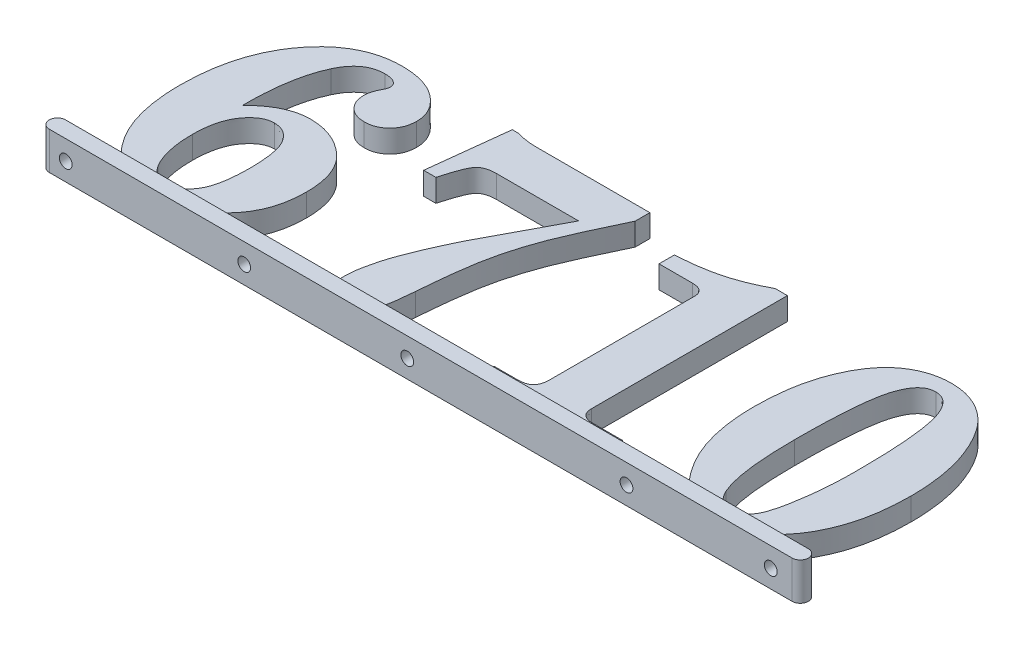
SolidWorks part; units mm, degrees
ref_plane "Front Plane" through (0, 0, 0) normal (0, 0, 1) x (1, 0, 0)
ref_plane "Top Plane" through (0, 0, 0) normal (0, 1, 0) x (1, 0, 0)
ref_plane "Right Plane" through (0, 0, 0) normal (1, 0, 0) x (0, 0, -1)
sketch "Sketch1" plane through (0, 0, 0) normal (0, 1, 0) x (1, 0, 0)
  text T0 "6710" font "Century Schoolbook" height 63.5
extrude "Boss-Extrude2" add sketch "Sketch1" along normal blind 6
sketch "Sketch2" plane through (0, 0, 0) normal (0, 1, 0) x (1, 0, 0)
  line L0 (-83.0987, -20.1486) -> (114.7244, -20.1486) construction
  line L1 (-83.0987, -17.9936) -> (114.7244, -17.9936)
  line L2 (-83.0987, -22.3035) -> (114.7244, -22.3035)
  arc A0 (-83.0987, -17.9936) -> (-83.0987, -22.3035) centre (-83.0987, -20.1486) ccw
  arc A1 (114.7244, -22.3035) -> (114.7244, -17.9936) centre (114.7244, -20.1486) ccw
  point P2 (15.8128, -20.1486)
extrude "Boss-Extrude3" add sketch "Sketch2" along normal blind 10
hole_wizard "M3 Clearance Hole1" positions "Sketch4" profile "Sketch3" hole size "M3" standard "ANSI Metric" end condition through all
sketch "Sketch4" plane through (0, 0, 17.9936) normal (0, 0, -1) x (-1, 0, 0)
  point P0 (78.7272, 4.7902)
  point P2 (31.1938, 4.7902)
  point P4 (-12.2208, 4.7902)
  point P6 (-70.6134, 4.7902)
  point P8 (-109.0334, 4.7902)
sketch "Sketch3" plane through (-78.7272, 4.7902, 17.9936) normal (1, 0, 0) x (0, 1, 0)
  line L0 (0, 0) -> (0, 4.3099)
  line L1 (0, 4.3099) -> (1.7, 4.3099)
  line L2 (1.7, 4.3099) -> (1.7, 0)
  line L5 (1.7, 0) -> (0, 0)
  line L11 (0, -6.35) -> (0, 107.95) construction
  dimension "Thru Hole Dia." = 3.4
  dimension "Thru Hole Depth" = 4.3099
